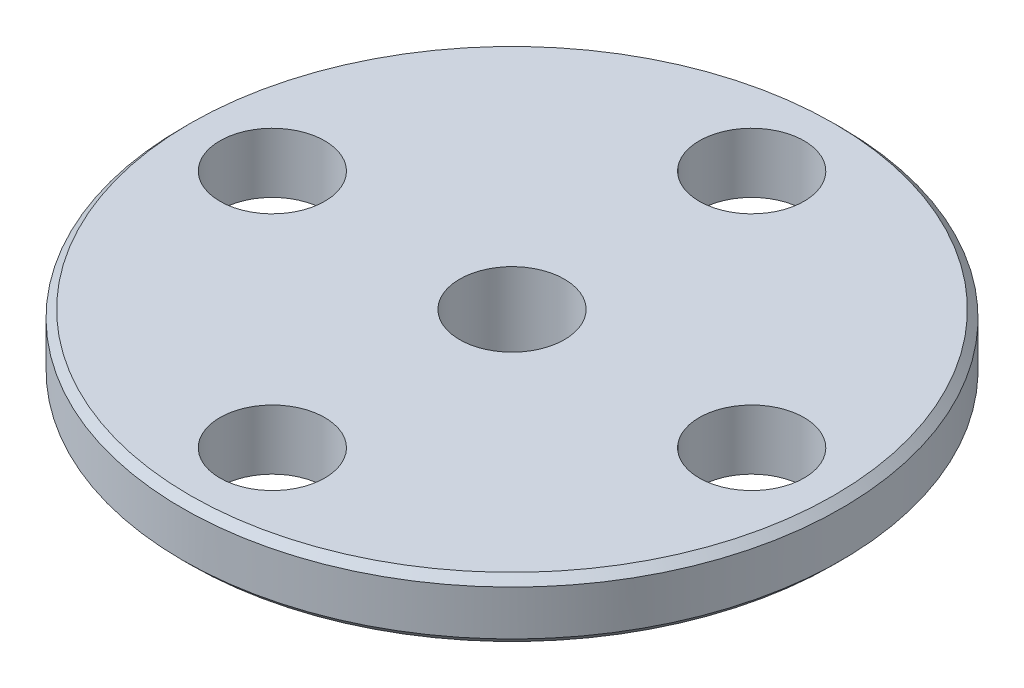
SolidWorks part; units mm, degrees
material "6061-T6 (SS)"
ref_plane "Front" through (0, 0, 0) normal (0, 0, 1) x (1, 0, 0)
ref_plane "Top" through (0, 0, 0) normal (0, 1, 0) x (1, 0, 0)
ref_plane "Right" through (0, 0, 0) normal (1, 0, 0) x (0, 0, -1)
ref_axis "side-side" through (80.9, 0, 0) along (-1, 0, 0)
ref_axis "up-down" through (0, 50, 0) along (0, -1, 0)
ref_axis "front-back" through (0, 0, -80.9) along (0, 0, 1)
sketch "Sketch2" plane through (0, 0, 0) normal (0, 0, 1) x (1, 0, 0)
  line L0 (0, 0) -> (0, 4.5938) construction
  line L1 (-11, 0) -> (-1.75, 0)
  line L2 (-11, 0) -> (-11, -2)
  line L3 (-4.4, -6.2) -> (-2.85, -6.2)
  line L4 (-1.75, 0) -> (-1.75, -3.2)
  line L7 (-11, -2) -> (-4.4, -2)
  line L8 (-4.4, -6.2) -> (-4.4, -2)
  line L10 (-2.85, -6.2) -> (-2.85, -3.2)
  line L11 (-2.85, -3.2) -> (-1.75, -3.2)
  point P10 (-0.6996, 0)
  dimension "D1" = 2
  dimension "D2" = 4.2
  dimension "D3" = 3
  dimension "D4" = 3.5
  dimension "D5" = 22
  dimension "D6" = 8.8
  dimension "D7" = 5.7
revolve "Revolve1" add sketch "Sketch2" angle 360 about L0
hole_wizard "Ø3.5 (3.5) Diameter Hole1" positions "Sketch3" profile "Sketch4" hole size "Ø3.5" standard "ANSI Metric" end condition through all
sketch "Sketch3" plane through (0, 0, 0) normal (0, 1, 0) x (1, 0, 0)
  arc A0 (-5.2213, 6.0611) -> (4.4206, 6.6677) centre (0, 0) cw construction
  point P0 (0, 8)
  point P2 (0, -8)
  point P4 (-8, 0)
  point P6 (8, 0)
  point P13 (0, 0)
  point P14 (0, 0)
  point P15 (0, 0)
  point P16 (0, 0)
  point P17 (0, 0)
  point P18 (0, 0)
  dimension "D1" = 8
sketch "Sketch4" plane through (0, 0, -8) normal (1, 0, 0) x (0, 0, 1)
  line L0 (0, 0) -> (0, 6.2)
  line L1 (0, 6.2) -> (1.75, 6.2)
  line L2 (1.75, 6.2) -> (1.75, 0)
  line L5 (1.75, 0) -> (0, 0)
  line L11 (0, -6.35) -> (0, 107.95) construction
  dimension "Thru Hole Dia." = 3.5
  dimension "Thru Hole Depth" = 6.2
chamfer "Chamfer1" distance 0.25 angle 45 3 edges at (0, -6.2, -4.4) (0, -2, -11) (0, 0, -11)
